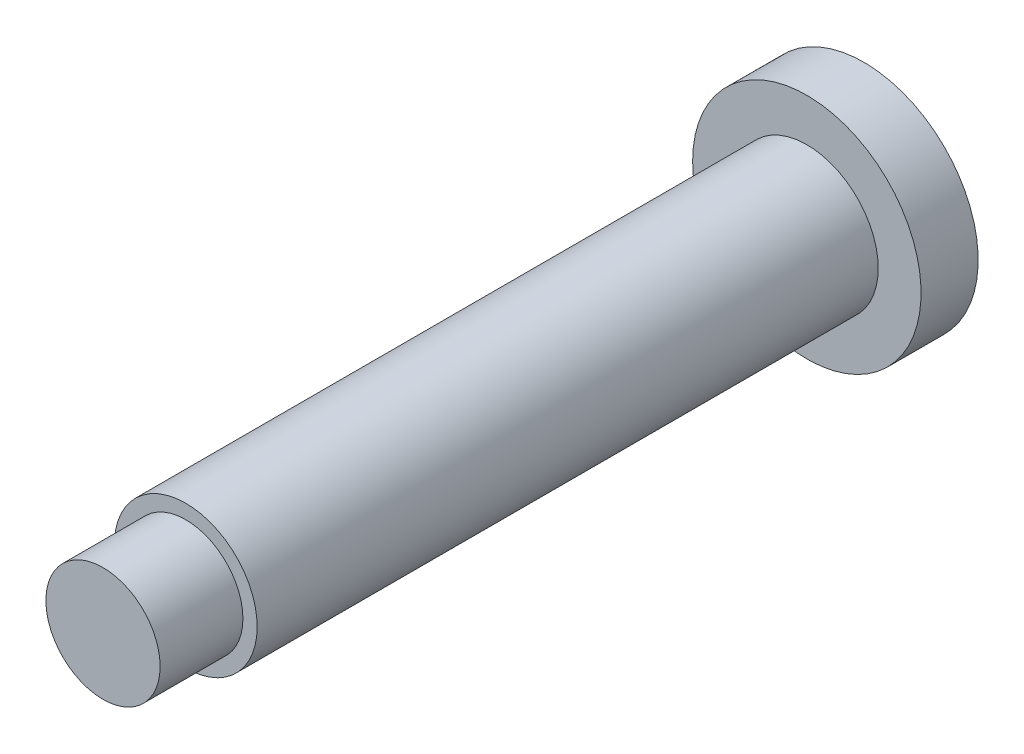
SolidWorks part; units mm, degrees
ref_plane "Front Plane" through (0, 0, 0) normal (1, 0, 0) x (0, 1, 0)
ref_plane "Top Plane" through (0, 0, 0) normal (0, 0, 1) x (0, 1, 0)
ref_plane "Right Plane" through (0, 0, 0) normal (0, 1, 0) x (-1, 0, 0)
sketch "Sketch1" plane through (0, 0, 0) normal (0, 0, 1) x (0, 1, 0)
  circle A0 centre (0, 0) radius 2.5
extrude "Boss-Extrude1" add sketch "Sketch1" along normal blind 21.75 contours A0
sketch "Sketch2" plane through (0, 0, 0) normal (0, 0, -1) x (1, 0, 0)
  circle A0 centre (0, 0) radius 4
extrude "Boss-Extrude2" add sketch "Sketch2" along normal blind 2
sketch "Sketch3" plane through (0, 0, -2) normal (0, 0, -1) x (1, 0, 0)
  circle A0 centre (0, 0) radius 2.05
extrude "Cut-Extrude1" cut sketch "Sketch3" against normal blind 3
sketch "Sketch4" plane through (0, 0, 21.75) normal (0, 0, 1) x (1, 0, 0)
  circle A0 centre (0, 0) radius 2
extrude "Boss-Extrude3" add sketch "Sketch4" along normal blind 2.9
